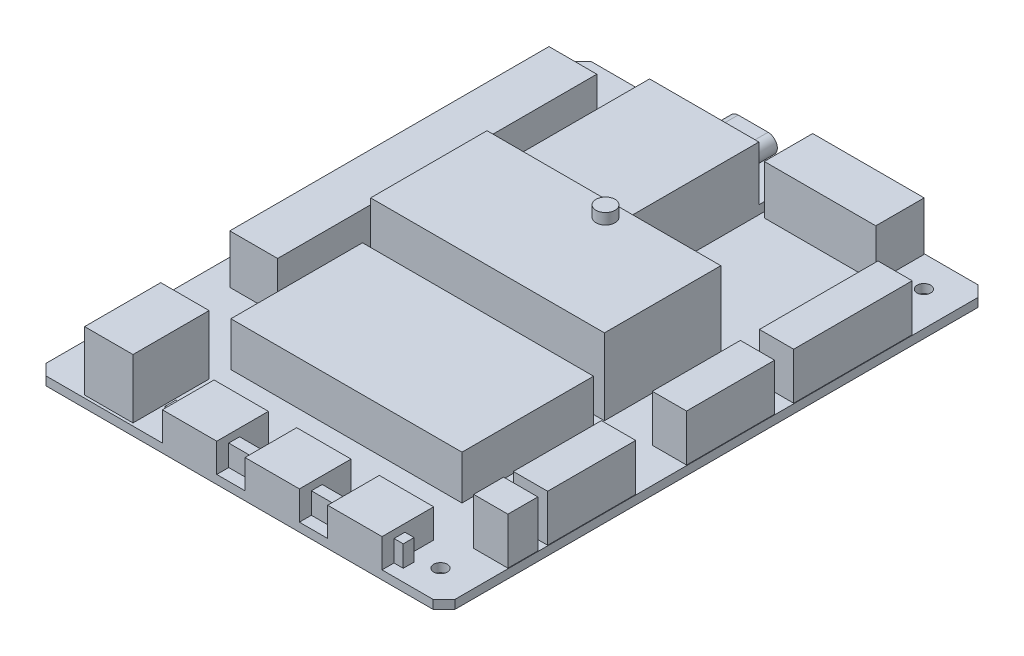
SolidWorks part; units mm, degrees
ref_plane "Front Plane" through (0, 0, 0) normal (0, 0, 1) x (1, 0, 0)
ref_plane "Top Plane" through (0, 0, 0) normal (0, 1, 0) x (1, 0, 0)
ref_plane "Right Plane" through (0, 0, 0) normal (1, 0, 0) x (0, 0, -1)
sketch "Sketch1" plane through (0, 0, 0) normal (0, 1, 0) x (1, 0, 0)
  line L1 (-37.6, -50.1) -> (37.6, -50.1)
  line L2 (-37.6, -50.1) -> (-37.6, 50.1)
  line L3 (-37.6, 50.1) -> (37.6, 50.1)
  line L4 (37.6, -50.1) -> (37.6, 50.1)
  line L5 (-37.6, -50.1) -> (37.6, 50.1) construction
  line L6 (-37.6, 50.1) -> (37.6, -50.1) construction
  point P0 (0, 0)
  dimension "D1" = 75.2
  dimension "D2" = 100.2
extrude "Boss-Extrude1" add sketch "Sketch1" along normal blind 1.6
chamfer "Chamfer1" distance 2 angle 45 4 edges at (-37.6, 0.8, -50.1) (37.6, 0.8, -50.1) (-37.6, 0.8, 50.1) (37.6, 0.8, 50.1)
sketch "Sketch2" plane through (0, 1.6, 0) normal (0, 1, 0) x (1, 0, 0)
  line L0 (-37.6, 48.1) -> (-37.6, -48.1) construction
  line L1 (-32.2, -44.45) -> (31.3, -44.45) construction
  line L2 (-32.2, -44.45) -> (-32.2, 44.45) construction
  line L3 (-32.2, 44.45) -> (31.3, 44.45) construction
  line L4 (31.3, -44.45) -> (31.3, 44.45) construction
  line L5 (-32.2, -44.45) -> (31.3, 44.45) construction
  line L6 (-32.2, 44.45) -> (31.3, -44.45) construction
  line L7 (37.6, -48.1) -> (37.6, 48.1) construction
  line L8 (-0.45, 0) -> (-0.45, -50.1) construction
  line L9 (-35.6, -50.1) -> (35.6, -50.1) construction
  line L10 (-0.45, 0) -> (-0.45, 50.1) construction
  line L11 (35.6, 50.1) -> (-35.6, 50.1) construction
  circle A0 centre (-32.2, 44.45) radius 1.25
  circle A1 centre (-32.2, -44.45) radius 1.25
  circle A2 centre (31.3, -44.45) radius 1.25
  circle A3 centre (31.3, 44.45) radius 1.25
  point P0 (-0.45, 0)
  dimension "D1" = 2.5
  dimension "D2" = 63.5
  dimension "D3" = 88.9
  dimension "D4" = 5.4
  dimension "D5" = 6.3
  dimension "D6" = 5.4
extrude "Cut-Extrude1" cut sketch "Sketch2" against normal through all
sketch "Sketch3" plane through (0, 1.6, 0) normal (0, 1, 0) x (1, 0, 0)
  line L0 (35.6, 50.1) -> (-35.6, 50.1) construction
  line L1 (-32.8, 39.6) -> (-24, 39.6)
  line L2 (-32.8, 39.6) -> (-32.8, -19.1)
  line L3 (-32.8, -19.1) -> (-24, -19.1)
  line L4 (-24, 39.6) -> (-24, -19.1)
  line L5 (-32.8, 39.6) -> (-24, -19.1) construction
  line L6 (-32.8, -19.1) -> (-24, 39.6) construction
  line L7 (5.3, 50) -> (25.8, 50)
  line L8 (5.3, 50) -> (5.3, 41.1)
  line L9 (5.3, 41.1) -> (25.8, 41.1)
  line L10 (25.8, 50) -> (25.8, 41.1)
  line L11 (31.2, 36.1) -> (37.5, 36.1)
  line L12 (31.2, 36.1) -> (31.2, 14.3)
  line L13 (31.2, 14.3) -> (37.5, 14.3)
  line L14 (37.5, 36.1) -> (37.5, 14.3)
  line L15 (31.2, 10.8) -> (37.5, 10.8)
  line L16 (31.2, 10.8) -> (31.2, -5.4)
  line L17 (31.2, -5.4) -> (37.5, -5.4)
  line L18 (37.5, 10.8) -> (37.5, -5.4)
  line L19 (31.2, -14.75) -> (37.5, -14.75)
  line L20 (31.2, -14.75) -> (31.2, -30.95)
  line L21 (31.2, -30.95) -> (37.5, -30.95)
  line L22 (37.5, -14.75) -> (37.5, -30.95)
  line L23 (31.2, -32.75) -> (37.5, -32.75)
  line L24 (31.2, -32.75) -> (31.2, -38.25)
  line L25 (31.2, -38.25) -> (37.5, -38.25)
  line L26 (37.5, -32.75) -> (37.5, -38.25)
  line L27 (-29, -35.6) -> (-20.1, -35.6)
  line L28 (-29, -35.6) -> (-29, -49.6)
  line L29 (-29, -49.6) -> (-20.1, -49.6)
  line L30 (-20.1, -35.6) -> (-20.1, -49.6)
  line L31 (-15.8, 49.1) -> (4.3, 49.1)
  line L32 (-15.8, 49.1) -> (-15.8, 17.1)
  line L33 (-15.8, 17.1) -> (4.3, 17.1)
  line L34 (4.3, 49.1) -> (4.3, 17.1)
  line L35 (-14.2, -40.6) -> (-4.2, -40.6)
  line L36 (-14.2, -40.6) -> (-14.2, -50.1)
  line L37 (-14.2, -50.1) -> (-4.2, -50.1)
  line L38 (-4.2, -40.6) -> (-4.2, -50.1)
  line L39 (1, -40.6) -> (11, -40.6)
  line L40 (1, -40.6) -> (1, -50.1)
  line L41 (1, -50.1) -> (11, -50.1)
  line L42 (11, -40.6) -> (11, -50.1)
  line L43 (16.2, -40.6) -> (26.2, -40.6)
  line L44 (16.2, -40.6) -> (16.2, -50.1)
  line L45 (16.2, -50.1) -> (26.2, -50.1)
  line L46 (26.2, -40.6) -> (26.2, -50.1)
  line L47 (-35.6, -50.1) -> (35.6, -50.1) construction
  line L48 (-37.6, 48.1) -> (-37.6, -48.1) construction
  line L49 (37.6, -48.1) -> (37.6, 48.1) construction
  point P0 (-28.4, 10.25)
  point P45 (-29.9002, 7.8476)
  point P54 (-21.854, 49.2708)
  point P55 (3.5761, 26.1254)
  point P56 (5.4635, -43.6086)
  point P57 (34.35, 10.8)
  line M53 (-35.6, -50.1) -> (35.6, -50.1)
  dimension "D1" = 8.8
  dimension "D2" = 58.7
  dimension "D3" = 10.5
  dimension "D4" = 31
  dimension "D5" = 4.8
  dimension "D6" = 20.5
  dimension "D7" = 8.9
  dimension "D8" = 0.1
  dimension "D9" = 11.8
  dimension "D10" = 1
  dimension "D11" = 20.1
  dimension "D12" = 1
  dimension "D13" = 32
  dimension "D14" = 0.5
  dimension "D15" = 8.9
  dimension "D16" = 14
  dimension "D17" = 8.6
  dimension "D18" = 10
  dimension "D19" = 9.5
  dimension "D20" = 5.2
  dimension "D21" = 5.2
  dimension "D22" = 11.4
  dimension "D23" = 5.9
  dimension "D24" = 0.1
  dimension "D25" = 6.3
  dimension "D26" = 21.8
  dimension "D27" = 16.2
  dimension "D28" = 16.2
  dimension "D29" = 5.5
  dimension "D30" = 3.5
  dimension "D31" = 9.35
  dimension "D32" = 14
  dimension "D33" = 1.8
  dimension "D34" = 11.85
extrude "Boss-Extrude2" add sketch "Sketch3" along normal blind 9 contours L4 L1 L2 L3 | L10 L7 L8 L9 region at (-28.4, 1.6, -10.25) region at (15.55, 1.6, -45.55)
extrude "Boss-Extrude3" add sketch "Sketch3<3>" along normal blind 1.6 contours L34 L31 L32 L33 region at (-5.75, 1.6, -33.1)
sketch "Sketch3<3>" plane through (0, 1.6, 0) normal (0, 1, 0) x (1, 0, 0) same geometry as "Sketch3"
extrude "Boss-Extrude4" add sketch "Sketch3<4>" along normal blind 8.6 contours L14 L11 L12 L13 | L18 L15 L16 L17 | L22 L19 L20 L21 | L26 L23 L24 L25 region at (34.35, 1.6, -25.2) region at (34.35, 1.6, -2.7) region at (34.35, 1.6, 22.85) region at (34.35, 1.6, 35.5)
sketch "Sketch3<4>" plane through (0, 1.6, 0) normal (0, 1, 0) x (1, 0, 0) same geometry as "Sketch3"
extrude "Boss-Extrude5" add sketch "Sketch3<5>" along normal blind 5.3 contours L38 L35 L36 M53 | L42 L39 L40 M53 | L46 L43 L44 M53 region at (21.2, 1.6, 45.35) region at (6, 1.6, 45.35) region at (-9.2, 1.6, 45.35)
sketch "Sketch3<5>" plane through (0, 1.6, 0) normal (0, 1, 0) x (1, 0, 0) same geometry as "Sketch3"
extrude "Boss-Extrude6" add sketch "Sketch3<6>" along normal blind 10.9 contours L30 L27 L28 L29 region at (-24.55, 1.6, 42.6)
sketch "Sketch3<6>" plane through (0, 1.6, 0) normal (0, 1, 0) x (1, 0, 0) same geometry as "Sketch3"
sketch "Sketch4" plane through (0, 0, -50.1) normal (0, 0, -1) x (-1, 0, 0)
  line L0 (5.75, 3.2) -> (5.75, 9.0575) construction
  line L1 (15.8, 3.2) -> (-4.3, 3.2) construction
  line L2 (8.5, 4.9) -> (3, 4.9) construction
  line L3 (8.5, 3.2) -> (3, 3.2)
  line L4 (8.5, 6.6) -> (3, 6.6)
  arc A0 (8.5, 3.2) -> (8.5, 6.6) centre (8.5, 4.9) ccw
  arc A1 (3, 6.6) -> (3, 3.2) centre (3, 4.9) ccw
  point P6 (5.75, 4.9)
  dimension "D2" = 8.9
  dimension "D1" = 3.4
extrude "Boss-Extrude7" add sketch "Sketch4" against normal blind 8
sketch "Sketch5" plane through (0, 1.6, 0) normal (0, 1, 0) x (1, 0, 0)
  line L0 (-4.2, -50.1) -> (1, -50.1) construction
  line L1 (-15.9, -45.9) -> (27.9, -45.9)
  line L2 (-15.9, -45.9) -> (-15.9, -47.9)
  line L3 (-15.9, -47.9) -> (27.9, -47.9)
  line L4 (27.9, -45.9) -> (27.9, -47.9)
  line L5 (-14.2, -40.6) -> (-14.2, -50.1) construction
  line L6 (26.2, -40.6) -> (26.2, -50.1) construction
  dimension "D1" = 2.2
  dimension "D2" = 2
  dimension "D3" = 1.7
  dimension "D4" = 1.7
extrude "Boss-Extrude8" add sketch "Sketch5" along normal blind 3.9
sketch "Sketch7" plane through (0, 1.6, 0) normal (0, 1, 0) x (1, 0, 0)
  line L0 (-35.6, -50.1) -> (-14.2, -50.1) construction
  line L1 (-20.1, 15.5) -> (22.9, 15.5)
  line L2 (-20.1, 15.5) -> (-20.1, -5.9)
  line L3 (-20.1, -5.9) -> (22.9, -5.9)
  line L4 (22.9, 15.5) -> (22.9, -5.9)
  line L5 (-19.6, -7.9) -> (22.9, -7.9)
  line L6 (-19.6, -7.9) -> (-19.6, -32.1)
  line L7 (-19.6, -32.1) -> (22.9, -32.1)
  line L8 (22.9, -7.9) -> (22.9, -32.1)
  line L9 (-37.6, 48.1) -> (-37.6, -48.1) construction
  line L10 (35.6, 50.1) -> (-35.6, 50.1) construction
  dimension "D1" = 24.2
  dimension "D2" = 42.5
  dimension "D3" = 18
  dimension "D4" = 18
  dimension "D5" = 21.4
  dimension "D6" = 43
  dimension "D7" = 34.6
extrude "Boss-Extrude9" add sketch "Sketch7" along normal blind 8.1 contours L8 L5 L6 L7 region at (1.65, 1.6, 20)
extrude "Boss-Extrude10" add sketch "Sketch7<3>" along normal blind 14 contours L4 L1 L2 L3 region at (1.4, 1.6, -4.8)
sketch "Sketch7<3>" plane through (0, 1.6, 0) normal (0, 1, 0) x (1, 0, 0) same geometry as "Sketch7"
sketch "Sketch8" plane through (0, 3.2, 0) normal (0, 1, 0) x (1, 0, 0)
  line L0 (4.3, 49.1) -> (4.3, 17.1) construction
  line L1 (-15.8, 17.1) -> (4.3, 17.1)
  line L2 (-15.8, 17.1) -> (-15.8, 41.1)
  line L3 (-15.8, 41.1) -> (4.3, 41.1)
  line L4 (4.3, 17.1) -> (4.3, 41.1)
  dimension "D1" = 24
extrude "Boss-Extrude11" add sketch "Sketch8" along normal blind 10
sketch "Sketch9" plane through (0, 15.6, 0) normal (0, 1, 0) x (1, 0, 0)
  line L0 (37.6, -48.1) -> (37.6, 48.1) construction
  line L1 (35.6, 50.1) -> (-35.6, 50.1) construction
  circle A0 centre (4.6, 12.6) radius 1.75
  dimension "D1" = 33
  dimension "D3" = 3.5
  dimension "D2" = 37.5
extrude "Boss-Extrude12" add sketch "Sketch9" along normal blind 2
